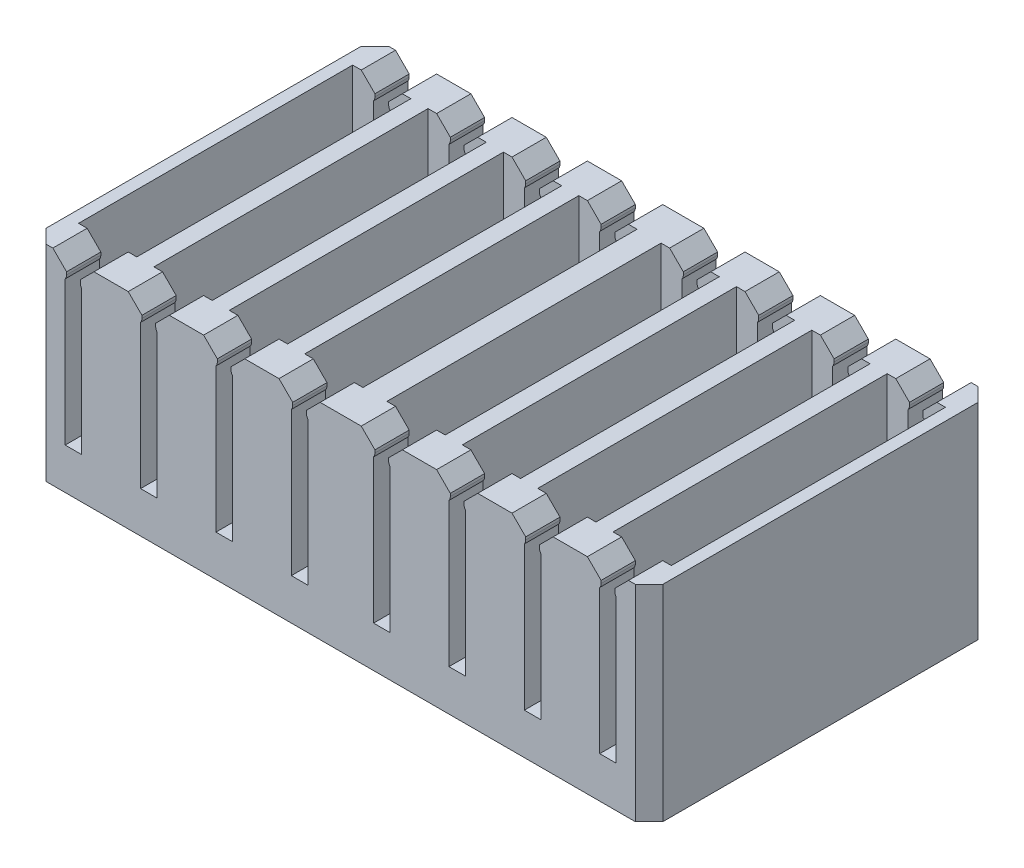
SolidWorks part; units mm, degrees
ref_plane "Front Plane" through (0, 0, 0) normal (0, 0, 1) x (1, 0, 0)
ref_plane "Top Plane" through (0, 0, 0) normal (0, 1, 0) x (1, 0, 0)
ref_plane "Right Plane" through (0, 0, 0) normal (1, 0, 0) x (0, 0, -1)
sketch "Sketch2" plane through (0, 0, 0) normal (0, 1, 0) x (1, 0, 0)
  line L1 (-22.5, 12.5) -> (22.5, 12.5)
  line L2 (-22.5, 12.5) -> (-22.5, -12.5)
  line L3 (-22.5, -12.5) -> (22.5, -12.5)
  line L4 (22.5, 12.5) -> (22.5, -12.5)
  line L5 (-22.5, 12.5) -> (22.5, -12.5) construction
  line L6 (-22.5, -12.5) -> (22.5, 12.5) construction
  point P0 (0, 0)
  dimension "D1" = 45
  dimension "D2" = 25
extrude "Boss-Extrude1" add sketch "Sketch2" along normal blind 15
sketch "Sketch4" plane through (0, 0, 12.5) normal (0, 0, 1) x (1, 0, 0)
  line L0 (-22.5, 15) -> (22.5, 15) construction
  line L1 (-20, 15) -> (-19, 15)
  line L2 (-20, 15) -> (-20, 3)
  line L3 (-20, 3) -> (-19, 3)
  line L4 (-19, 15) -> (-19, 3)
  line L5 (-20, 15) -> (-19, 3) construction
  line L6 (-20, 3) -> (-19, 15) construction
  line L7 (-22.5, 15) -> (-22.5, 0) construction
  line L38 (-20, 15) -> (-20, 13.5) construction
  line L39 (-19.5, 15) -> (-19.5, 3) construction
  line L40 (-20, 13.5) -> (-20.1, 13.5)
  line L41 (-20, 13.5) -> (-20, 3)
  line L42 (-20, 3) -> (-20.1, 3)
  line L43 (-20.1, 13.5) -> (-20.1, 3)
  line L44 (-20, 13.5) -> (-20.1, 3) construction
  line L45 (-20, 3) -> (-20.1, 13.5) construction
  line L46 (-19, 3) -> (-18.9, 3)
  line L47 (-18.9, 13.5) -> (-18.9, 3)
  line L48 (-19, 13.5) -> (-18.9, 13.5)
  line L49 (-19, 13.5) -> (-19, 3)
  point P4 (-19.5, 9)
  point P42 (-20.05, 8.25)
  dimension "D1" = 12
  dimension "D2" = 1
  dimension "D3" = 2.5
  dimension "D5" = 0.1
  dimension "D6" = 10.5
extrude "Cut-Extrude1" cut sketch "Sketch4" against normal up to next contours L2 L1 L4 L3 | L41 L40 L43 L42 | L46 L47 L48 L49
pattern_linear "LPattern1" count 4 spacing 5.5 along (1, 0, 0) of "Cut-Extrude1"
mirror "Mirror1" about plane through (0, 0, 0) normal (1, 0, 0) of "LPattern1"
sketch "Sketch9" plane through (0, 15, 0) normal (0, 1, 0) x (1, 0, 0)
  line L0 (-20, 0) -> (-19, 0) construction
  line L1 (-20, 12.5) -> (-20, -12.5) construction
  line L2 (-19, 12.5) -> (-19, -12.5) construction
  line L4 (-21.625, 10) -> (-17.375, 10)
  line L5 (-21.625, 10) -> (-21.625, -10)
  line L6 (-21.625, -10) -> (-17.375, -10)
  line L7 (-17.375, 10) -> (-17.375, -10)
  line L8 (-21.625, 10) -> (-17.375, -10) construction
  line L9 (-21.625, -10) -> (-17.375, 10) construction
  point P6 (-19.5, 0)
  dimension "D1" = 4.25
  dimension "D2" = 20
extrude "Cut-Extrude3" cut sketch "Sketch9" against normal blind 12
pattern_linear "LPattern2" count 4 spacing 5.5 along (1, 0, 0) of "Cut-Extrude3"
mirror "Mirror2" about plane through (0, 0, 0) normal (1, 0, 0) of "LPattern2"
chamfer "Chamfer1" distance 1 angle 45 4 edges at (-22.5, 7.5, -12.5) (22.5, 7.5, -12.5) (22.5, 7.5, 12.5) (-22.5, 7.5, 12.5)
chamfer "Chamfer2" distance 1 angle 45 32 edges at (20, 15, 11.25) (19, 15, 11.25) (14.5, 15, 11.25) (13.5, 15, 11.25) (9, 15, 11.25) (8, 15, 11.25) (3.5, 15, 11.25) (2.5, 15, 11.25) (-2.5, 15, 11.25) (-3.5, 15, 11.25) (-8, 15, 11.25) (-9, 15, 11.25) (-13.5, 15, 11.25) (-14.5, 15, 11.25) (-19, 15, 11.25) (-20, 15, 11.25) (20, 15, -11.25) (19, 15, -11.25) (14.5, 15, -11.25) (13.5, 15, -11.25) (9, 15, -11.25) (8, 15, -11.25) (3.5, 15, -11.25) (2.5, 15, -11.25) (-2.5, 15, -11.25) (-3.5, 15, -11.25) (-8, 15, -11.25) (-9, 15, -11.25) (-13.5, 15, -11.25) (-14.5, 15, -11.25) (-19, 15, -11.25) (-20, 15, -11.25)
fillet "Fillet1" radius 0.5 31 edges at (-20, 13.5, -11.25) (-19, 13.5, -11.25) (-14.5, 13.5, -11.25) (-13.5, 13.5, -11.25) (-9, 13.5, -11.25) (-8, 13.5, -11.25) (-3.5, 13.5, -11.25) (-2.5, 13.5, -11.25) (3.5, 13.5, -11.25) (2.5, 13.5, -11.25) (8, 13.5, -11.25) (13.5, 13.5, -11.25) (9, 13.5, -11.25) (14.5, 13.5, -11.25) (19, 13.5, -11.25) (20, 13.5, 11.25) (19, 13.5, 11.25) (14.5, 13.5, 11.25) (13.5, 13.5, 11.25) (9, 13.5, 11.25) (8, 13.5, 11.25) (3.5, 13.5, 11.25) (2.5, 13.5, 11.25) (-2.5, 13.5, 11.25) (-3.5, 13.5, 11.25) (-8, 13.5, 11.25) (-9, 13.5, 11.25) (-13.5, 13.5, 11.25) (-14.5, 13.5, 11.25) (-19, 13.5, 11.25) (-20, 13.5, 11.25)
sketch "Sketch10" plane through (0, 0, 0) normal (0, -1, 0) x (1, 0, 0)
  line L0 (-22.5, 0) -> (-10, 0) construction
  line L1 (-22.5, -11.5) -> (-22.5, 11.5) construction
  line L2 (8.25, 0) -> (-8.25, 0) construction
  line L3 (0, -8.25) -> (0, 8.25) construction
  circle A0 centre (-10, 0) radius 6.11
  circle A1 centre (10, 0) radius 6.11
  dimension "D2" = 12.22
  dimension "D1" = 12.5
extrude "Boss-Extrude2" add sketch "Sketch10" along normal blind 3.5
fillet "Fillet2" radius 1 2 edges at (10, -3.5, 6.11) (-10, -3.5, -6.11)
